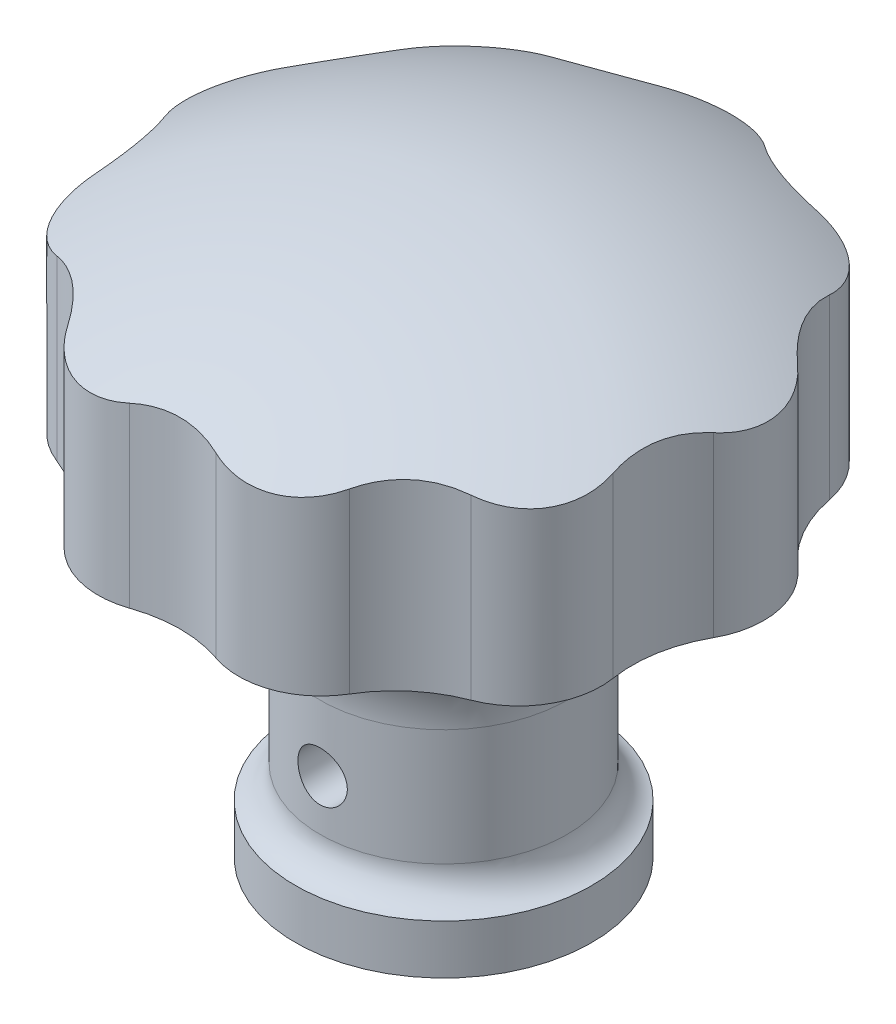
SolidWorks part; units mm, degrees
ref_plane "前视基准面" through (0, 0, 0) normal (0, 0, 1) x (1, 0, 0)
ref_plane "上视基准面" through (0, 0, 0) normal (0, 1, 0) x (1, 0, 0)
ref_plane "右视基准面" through (0, 0, 0) normal (1, 0, 0) x (0, 0, -1)
sketch "草图1" plane through (0, 0, 0) normal (0, 0, 1) x (1, 0, 0)
  line L0 (0, 0) -> (0, 106.5849) construction
  line L1 (0, -55) -> (0, 55) construction
  line L2 (0, 0) -> (9, 0)
  line L3 (55, 0) -> (-55, 0) construction
  line L4 (9, 0) -> (9, 3)
  line L5 (9, 3) -> (7.5, 3)
  line L6 (7.5, 3) -> (7.5, 12)
  line L7 (15.5, 20) -> (17.5, 20)
  line L8 (17.5, 20) -> (17.5, 30.3109)
  line L9 (0, 0) -> (0, 35)
  arc A0 (17.5, 30.3109) -> (0, 35) centre (0, 0) ccw
  arc A1 (7.5, 12) -> (15.5, 20) centre (15.5, 12) cw
  point P15 (0, 41.886)
  point P16 (17.5, 33.429)
  point P17 (7.5, 19.5512)
  dimension "D1" = 9
  dimension "D6" = 35
  dimension "D8" = 8
  dimension "D2" = 15
  dimension "D3" = 35
  dimension "D4" = 3
  dimension "D5" = 35
  dimension "D7" = 20
revolve "旋转1" add sketch "草图1" angle 360 about L0
fillet "圆角1" radius 2 1 edges at (0, 3, -7.5)
sketch "草图2" plane through (0, 0, 0) normal (0, -1, 0) x (1, 0, 0)
  circle A0 centre (0, 0) radius 4
  dimension "D1" = 8
extrude "切除-拉伸1" cut sketch "草图2" against normal blind 20
sketch "草图3" plane through (0, 0, 0) normal (0, 0, 1) x (1, 0, 0)
  line L0 (0, -19.25) -> (0, 19.25) construction
  line L1 (19.25, 0) -> (-19.25, 0) construction
  circle A0 centre (0, 8) radius 1.5
  dimension "D1" = 3
  dimension "D2" = 8
extrude "切除-拉伸2" cut sketch "草图3" against normal through all both and the other way through all
chamfer "倒角1" distance 0.5 angle 45 1 edges at (0, 0, -4)
sketch "草图4" plane through (0, 0, 0) normal (0, 1, 0) x (1, 0, 0)
  line L0 (0, -16) -> (0, -17.5) construction
  line L2 (0, -19.25) -> (0, 19.25) construction
  arc A0 (2.625, -16.4429) -> (-2.625, -16.4429) centre (0, -24) ccw
  arc A1 (2.625, -16.4429) -> (8.5584, -14.2833) centre (4.2656, -11.7198) ccw
  circle A2 centre (0, 0) radius 17.5 construction
  arc A3 (-8.5584, -14.2833) -> (-12.5802, -10.9087) centre (-15.4269, -18.3851) ccw
  arc A4 (-15.7373, -5.4404) -> (-16.649, -0.2702) centre (-23.6354, -4.1676) ccw
  arc A5 (-15.5525, 5.9481) -> (-12.9275, 10.4948) centre (-20.7846, 12) ccw
  arc A6 (-8.0905, 14.5535) -> (-3.1571, 16.3491) centre (-8.2085, 22.5526) ccw
  arc A7 (3.1571, 16.3491) -> (8.0905, 14.5535) centre (8.2085, 22.5526) ccw
  arc A8 (12.9275, 10.4948) -> (15.5525, 5.9481) centre (20.7846, 12) ccw
  arc A9 (16.649, -0.2702) -> (15.7373, -5.4404) centre (23.6354, -4.1676) ccw
  arc A10 (12.5802, -10.9087) -> (8.5584, -14.2833) centre (15.4269, -18.3851) ccw
  arc A11 (-8.5584, -14.2833) -> (-2.625, -16.4429) centre (-4.2656, -11.7198) ccw
  arc A12 (-15.7373, -5.4404) -> (-12.5802, -10.9087) centre (-10.801, -6.236) ccw
  arc A13 (-15.5525, 5.9481) -> (-16.649, -0.2702) centre (-12.2824, 2.1657) ccw
  arc A14 (-8.0905, 14.5535) -> (-12.9275, 10.4948) centre (-8.0168, 9.554) ccw
  arc A16 (12.9275, 10.4948) -> (8.0905, 14.5535) centre (8.0168, 9.554) ccw
  arc A17 (16.649, -0.2702) -> (15.5525, 5.9481) centre (12.2824, 2.1657) ccw
  arc A18 (12.5802, -10.9087) -> (15.7373, -5.4404) centre (10.801, -6.236) ccw
  arc A26 (3.1571, 16.3491) -> (-3.1571, 16.3491) centre (0, 12.4719) ccw
  arc A28 (-3.1162, 8.5618) -> (3.1162, 8.5618) centre (0, 12.4719) ccw [skipped]
  dimension "D1" = 16
  dimension "D3" = 10
  dimension "D4" = 9
  dimension "D5" = 9
  dimension "D2" = 24
extrude "切除-拉伸3" cut sketch "草图4" along normal through all both and the other way through all flip side to cut
